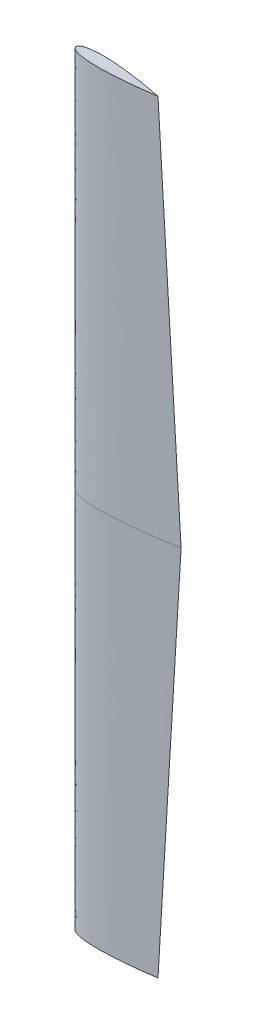
SolidWorks part; units mm, degrees
ref_plane "Front Plane" through (0, 0, 0) normal (0, 0, 1) x (1, 0, 0)
ref_plane "Top Plane" through (0, 0, 0) normal (0, 1, 0) x (1, 0, 0)
ref_plane "Right Plane" through (0, 0, 0) normal (1, 0, 0) x (0, 0, -1)
sketch "rootSketch" plane through (0, 0, 0) normal (0, 1, 0) x (1, 0, 0)
  line L0 (0, 0) -> (1500, 0) construction
  line L2 (137.5, -41.25) -> (137.5, 41.25) construction
  line L3 (0, 0) -> (550, 0) construction
  spline S0 degree 4 poles (0, 0) (-0.0002, 0.5984) (0.0567, 1.5657) (0.2758, 2.9641) (0.8226, 4.783) (1.5554, 6.4718) (2.6286, 8.3132) (4.15, 10.3394) (6.3375, 12.6439) (9.5808, 15.3558) (14.4955, 18.5934) (21.9815, 22.4137) (33.5898, 26.8869) (51.0146, 31.717) (76.9525, 36.5218) (110.4071, 39.9858) (144.1442, 41.3457) (175.9798, 41.3412) (207.8008, 40.5208) (234.2981, 39.2509) (260.7672, 37.5107) (287.2069, 35.3768) (308.3405, 33.4599) (329.4561, 31.3537) (350.5537, 29.0753) (368.9985, 26.9421) (384.7971, 25.0199) (397.955, 23.3576) (408.477, 21.9921) (421.6232, 20.2411) (437.39, 18.0697) (455.7689, 15.4347) (476.7548, 12.281) (495.0946, 9.3938) (509.495, 7.0363) (519.9529, 5.2764) (525.8458, 4.2686) (529.7425, 3.5958) (533.0627, 3.0173) (535.5459, 2.5832) (539.1156, 1.9525) (542.393, 1.3729) (547.5735, 0.4408) (550.9027, -0.1629) (555.289, -0.9656) (558.5613, -1.5705) (562.0766, -2.2247) (565.4861, -2.8651) (569.8025, -3.6822) (574.9524, -4.6683) (580.9745, -5.8375) (587.8418, -7.1939) (594.7112, -8.5743) (599.8557, -9.6263) (603.2861, -10.3361) (604.9999, -10.6929) knots 0 0 0 0 0 0.003841 0.006235 0.009072 0.012193 0.015657 0.019917 0.025339 0.032593 0.042799 0.057705 0.079311 0.112503 0.158973 0.227236 0.2955 0.329632 0.363764 0.432028 0.46616 0.500292 0.534424 0.568556 0.602688 0.63682 0.653886 0.670952 0.688018 0.705084 0.739215 0.773347 0.807479 0.841611 0.858677 0.86721 0.875743 0.88001 0.884276 0.888543 0.892809 0.901342 0.909875 0.915508 0.921141 0.926774 0.932406 0.938039 0.943672 0.954938 0.966203 0.977469 0.988734 1 1 1 1 1 construction
  spline S1 degree 4 poles (0, 0) (-0.0002, 0.5984) (0.0567, 1.5657) (0.2758, 2.9641) (0.8226, 4.783) (1.5554, 6.4718) (2.6286, 8.3132) (4.15, 10.3394) (6.3375, 12.6439) (9.5808, 15.3558) (14.4955, 18.5934) (21.9815, 22.4137) (33.5898, 26.8869) (51.0146, 31.717) (76.9525, 36.5218) (110.4071, 39.9858) (144.1442, 41.3457) (175.9798, 41.3412) (207.8008, 40.5208) (234.2981, 39.2509) (260.7672, 37.5107) (287.2069, 35.3768) (308.3405, 33.4599) (329.4561, 31.3537) (350.5537, 29.0753) (368.9985, 26.9421) (384.7971, 25.0199) (397.955, 23.3576) (408.477, 21.9921) (421.6232, 20.2411) (437.39, 18.0697) (455.7689, 15.4347) (476.7548, 12.281) (495.0946, 9.3938) (509.495, 7.0363) (519.9529, 5.2764) (525.8458, 4.2686) (529.7425, 3.5958) (533.0627, 3.0173) (535.5459, 2.5832) (539.1156, 1.9525) (542.393, 1.3729) (546.4913, 0.6355) (548.8127, 0.2157) (550, 0) knots 0 0 0 0 0 0.003841 0.006235 0.009072 0.012193 0.015657 0.019917 0.025339 0.032593 0.042799 0.057705 0.079311 0.112503 0.158973 0.227236 0.2955 0.329632 0.363764 0.432028 0.46616 0.500292 0.534424 0.568556 0.602688 0.63682 0.653886 0.670952 0.688018 0.705084 0.739215 0.773347 0.807479 0.841611 0.858677 0.86721 0.875743 0.88001 0.884276 0.888543 0.892809 0.901342 0.909875 0.909875 0.909875 0.909875 0.909875
  spline S2 degree 4 poles (0, 0) (-0.0002, -0.5984) (0.0567, -1.5657) (0.2758, -2.9641) (0.8226, -4.783) (1.5554, -6.4718) (2.6286, -8.3132) (4.15, -10.3394) (6.3375, -12.6439) (9.5808, -15.3558) (14.4955, -18.5934) (21.9815, -22.4137) (33.5898, -26.8869) (51.0146, -31.717) (76.9525, -36.5218) (110.4071, -39.9858) (144.1442, -41.3457) (175.9798, -41.3412) (207.8008, -40.5208) (234.2981, -39.2509) (260.7672, -37.5107) (287.2069, -35.3768) (308.3405, -33.4599) (329.4561, -31.3537) (350.5537, -29.0753) (368.9985, -26.9421) (384.7971, -25.0199) (397.955, -23.3576) (408.477, -21.9921) (421.6232, -20.2411) (437.39, -18.0697) (455.7689, -15.4347) (476.7548, -12.281) (495.0946, -9.3938) (509.495, -7.0363) (519.9529, -5.2764) (525.8458, -4.2686) (529.7425, -3.5958) (533.0627, -3.0173) (535.5459, -2.5832) (539.1156, -1.9525) (542.393, -1.3729) (547.5735, -0.4408) (550.9027, 0.1629) (555.289, 0.9656) (558.5613, 1.5705) (562.0766, 2.2247) (565.4861, 2.8651) (569.8025, 3.6822) (574.9524, 4.6683) (580.9745, 5.8375) (587.8418, 7.1939) (594.7112, 8.5743) (599.8557, 9.6263) (603.2861, 10.3361) (604.9999, 10.6929) knots 0 0 0 0 0 0.003841 0.006235 0.009072 0.012193 0.015657 0.019917 0.025339 0.032593 0.042799 0.057705 0.079311 0.112503 0.158973 0.227236 0.2955 0.329632 0.363764 0.432028 0.46616 0.500292 0.534424 0.568556 0.602688 0.63682 0.653886 0.670952 0.688018 0.705084 0.739215 0.773347 0.807479 0.841611 0.858677 0.86721 0.875743 0.88001 0.884276 0.888543 0.892809 0.901342 0.909875 0.915508 0.921141 0.926774 0.932406 0.938039 0.943672 0.954938 0.966203 0.977469 0.988734 1 1 1 1 1 construction
  spline S3 degree 4 poles (0, 0) (-0.0002, -0.5984) (0.0567, -1.5657) (0.2758, -2.9641) (0.8226, -4.783) (1.5554, -6.4718) (2.6286, -8.3132) (4.15, -10.3394) (6.3375, -12.6439) (9.5808, -15.3558) (14.4955, -18.5934) (21.9815, -22.4137) (33.5898, -26.8869) (51.0146, -31.717) (76.9525, -36.5218) (110.4071, -39.9858) (144.1442, -41.3457) (175.9798, -41.3412) (207.8008, -40.5208) (234.2981, -39.2509) (260.7672, -37.5107) (287.2069, -35.3768) (308.3405, -33.4599) (329.4561, -31.3537) (350.5537, -29.0753) (368.9985, -26.9421) (384.7971, -25.0199) (397.955, -23.3576) (408.477, -21.9921) (421.6232, -20.2411) (437.39, -18.0697) (455.7689, -15.4347) (476.7548, -12.281) (495.0946, -9.3938) (509.495, -7.0363) (519.9529, -5.2764) (525.8458, -4.2686) (529.7425, -3.5958) (533.0627, -3.0173) (535.5459, -2.5832) (539.1156, -1.9525) (542.393, -1.3729) (546.4913, -0.6355) (548.8127, -0.2157) (550, 0) knots 0 0 0 0 0 0.003841 0.006235 0.009072 0.012193 0.015657 0.019917 0.025339 0.032593 0.042799 0.057705 0.079311 0.112503 0.158973 0.227236 0.2955 0.329632 0.363764 0.432028 0.46616 0.500292 0.534424 0.568556 0.602688 0.63682 0.653886 0.670952 0.688018 0.705084 0.739215 0.773347 0.807479 0.841611 0.858677 0.86721 0.875743 0.88001 0.884276 0.888543 0.892809 0.901342 0.909875 0.909875 0.909875 0.909875 0.909875
  point P10 (137.5, 0)
  dimension "incidenceAngle" = 0
  dimension "rootChord" = 550
  dimension "rootQuarterChord" = 137.5
  dimension "rootMaxThickness" = 82.5
ref_plane "Plane1" through (0, 1999.998, 0) normal (0, 1, 0) x (1, 0, 0)
sketch "tipSketch" plane through (0, 1999.998, 0) normal (0, 1, 0) x (1, 0, 0)
  line L0 (218.7894, 0) -> (520.1012, 0) construction
  line L3 (0, 0) -> (439.861, -11.0572) construction
  line L4 (109.136, -35.7539) -> (110.7946, 30.2253) construction
  spline S0 degree 4 poles (0, 0) (-0.0002, 0.4799) (0.0456, 1.2558) (0.2213, 2.3695) (0.6579, 3.8074) (1.2415, 5.1394) (2.0932, 6.583) (3.2989, 8.1632) (5.0276, 9.9467) (7.5719, 12.0224) (11.4477, 14.4998) (17.3746, 17.4012) (26.5746, 20.7437) (40.3867, 24.2587) (61.0632, 27.6137) (87.8004, 29.7482) (119.0763, 30.2504) (148.9069, 29.2696) (174.4344, 27.6771) (195.6772, 25.9397) (212.6521, 24.3361) (229.6081, 22.5432) (246.5456, 20.5825) (263.4645, 18.4705) (280.3662, 16.221) (295.1391, 14.1416) (307.7921, 12.2843) (318.327, 10.6888) (326.7541, 9.3833) (337.2749, 7.7178) (349.9046, 5.6607) (364.6022, 3.1846) (381.4182, 0.2341) (396.0609, -2.4384) (408.6785, -4.8221) (419.0533, -6.8347) (426.5408, -8.32) (432.4883, -9.518) (438.6715, -10.7845) (442.4872, -11.5748) (448.6722, -12.8694) (453.5332, -13.9082) (459.43, -15.1786) (464.6859, -16.3343) (470.343, -17.5913) (475.7161, -18.8084) (479.9213, -19.772) (482.6133, -20.398) (484.0029, -20.7217) knots 0 0 0 0 0 0.003846 0.006245 0.009023 0.012045 0.015501 0.01968 0.024954 0.031954 0.041824 0.056556 0.077861 0.110456 0.156157 0.224645 0.293132 0.36162 0.395864 0.430108 0.464352 0.498596 0.53284 0.567084 0.601327 0.635571 0.652693 0.669815 0.686937 0.704059 0.738303 0.772547 0.806791 0.841035 0.858157 0.875279 0.892401 0.900962 0.909523 0.920832 0.932142 0.943452 0.954761 0.966071 0.977381 0.98869 1 1 1 1 1 construction
  spline S1 degree 4 poles (0, 0) (-0.0002, 0.4799) (0.0456, 1.2558) (0.2213, 2.3695) (0.6579, 3.8074) (1.2415, 5.1394) (2.0932, 6.583) (3.2989, 8.1632) (5.0276, 9.9467) (7.5719, 12.0224) (11.4477, 14.4998) (17.3746, 17.4012) (26.5746, 20.7437) (40.3867, 24.2587) (61.0632, 27.6137) (87.8004, 29.7482) (119.0763, 30.2504) (148.9069, 29.2696) (174.4344, 27.6771) (195.6772, 25.9397) (212.6521, 24.3361) (229.6081, 22.5432) (246.5456, 20.5825) (263.4645, 18.4705) (280.3662, 16.221) (295.1391, 14.1416) (307.7921, 12.2843) (318.327, 10.6888) (326.7541, 9.3833) (337.2749, 7.7178) (349.9046, 5.6607) (364.6022, 3.1846) (381.4182, 0.2341) (396.0609, -2.4384) (408.6785, -4.8221) (419.0533, -6.8347) (426.5408, -8.32) (432.4883, -9.518) (437.1364, -10.47) (439.0509, -10.8644) (440, -11.0607) knots 0 0 0 0 0 0.003846 0.006245 0.009023 0.012045 0.015501 0.01968 0.024954 0.031954 0.041824 0.056556 0.077861 0.110456 0.156157 0.224645 0.293132 0.36162 0.395864 0.430108 0.464352 0.498596 0.53284 0.567084 0.601327 0.635571 0.652693 0.669815 0.686937 0.704059 0.738303 0.772547 0.806791 0.841035 0.858157 0.875279 0.892401 0.900962 0.909523 0.909523 0.909523 0.909523 0.909523
  spline S2 degree 4 poles (0, 0) (-0.0243, -0.4792) (-0.0175, -1.2565) (0.102, -2.3776) (0.4657, -3.8356) (0.9817, -5.1953) (1.7598, -6.6799) (2.8846, -8.3186) (4.5214, -10.1867) (6.9583, -12.3877) (10.7048, -15.0566) (16.4783, -18.2522) (25.4988, -22.0527) (39.1168, -26.2572) (59.5987, -30.6469) (86.1948, -34.1221) (117.406, -36.1951) (147.2482, -36.7144) (172.8235, -36.4064) (194.1267, -35.7386) (211.1608, -34.99) (228.1855, -34.0512) (245.2, -32.944) (262.2037, -31.6848) (279.1971, -30.2873) (294.0558, -28.9528) (306.7861, -27.7336) (317.3879, -26.6694) (325.8699, -25.789) (336.4611, -24.6542) (349.1782, -23.2343) (363.9817, -21.4998) (380.9247, -19.3979) (395.6832, -17.4645) (408.4046, -15.7178) (418.8674, -14.229) (426.4201, -13.1218) (432.4203, -12.2241) (438.6593, -11.2699) (442.5099, -10.6723) (448.7521, -9.6901) (453.6592, -8.8968) (459.6124, -7.9243) (464.9197, -7.0341) (470.6328, -6.063) (476.0602, -5.1174) (480.3086, -4.3663) (483.0286, -3.8763) (484.4327, -3.6229) knots 0 0 0 0 0 0.003846 0.006245 0.009023 0.012045 0.015501 0.01968 0.024954 0.031954 0.041824 0.056556 0.077861 0.110456 0.156157 0.224645 0.293132 0.36162 0.395864 0.430108 0.464352 0.498596 0.53284 0.567084 0.601327 0.635571 0.652693 0.669815 0.686937 0.704059 0.738303 0.772547 0.806791 0.841035 0.858157 0.875279 0.892401 0.900962 0.909523 0.920832 0.932142 0.943452 0.954761 0.966071 0.977381 0.98869 1 1 1 1 1 construction
  spline S3 degree 4 poles (0, 0) (-0.0243, -0.4792) (-0.0175, -1.2565) (0.102, -2.3776) (0.4657, -3.8356) (0.9817, -5.1953) (1.7598, -6.6799) (2.8846, -8.3186) (4.5214, -10.1867) (6.9583, -12.3877) (10.7048, -15.0566) (16.4783, -18.2522) (25.4988, -22.0527) (39.1168, -26.2572) (59.5987, -30.6469) (86.1948, -34.1221) (117.406, -36.1951) (147.2482, -36.7144) (172.8235, -36.4064) (194.1267, -35.7386) (211.1608, -34.99) (228.1855, -34.0512) (245.2, -32.944) (262.2037, -31.6848) (279.1971, -30.2873) (294.0558, -28.9528) (306.7861, -27.7336) (317.3879, -26.6694) (325.8699, -25.789) (336.4611, -24.6542) (349.1782, -23.2343) (363.9817, -21.4998) (380.9247, -19.3979) (395.6832, -17.4645) (408.4046, -15.7178) (418.8674, -14.229) (426.4201, -13.1218) (432.4203, -12.2241) (437.1103, -11.5068) (439.0422, -11.2091) (440, -11.0607) knots 0 0 0 0 0 0.003846 0.006245 0.009023 0.012045 0.015501 0.01968 0.024954 0.031954 0.041824 0.056556 0.077861 0.110456 0.156157 0.224645 0.293132 0.36162 0.395864 0.430108 0.464352 0.498596 0.53284 0.567084 0.601327 0.635571 0.652693 0.669815 0.686937 0.704059 0.738303 0.772547 0.806791 0.841035 0.858157 0.875279 0.892401 0.900962 0.909523 0.909523 0.909523 0.909523 0.909523
  point P10 (109.9653, -2.7643)
  dimension "incidenceAngle" = 1.44
  dimension "tipChord" = 440
  dimension "tipQuarterChord" = 110
  dimension "tipMaxThickness" = 66
  dimension "sweepOffset" = 0
loft "Loft1" add profiles "rootSketch", "tipSketch" connector at (0, 0, 0) connector at (0, 1999.998, 0)
mirror "Mirror1" about plane through (0, 0, 0) normal (0, 1, 0) of "Loft1"
ref_plane "Plane2" through (550, 0, 0) normal (1, 0, 0) x (0, 0, -1)
sketch "elevatorSketch" plane through (0, 0, 0) normal (0, 0, 1) x (1, 0, 0)
  line L0 (333.9978, 0.1319) -> (284.6342, 1495.9985)
  line L1 (0, 1499.9985) -> (280.5, 1499.9985) construction
  line L2 (0, 0) -> (330, 0) construction
  line L3 (0, 0) -> (550, 0) construction
  line L4 (330, 0) -> (280.5, 1499.9985)
  line L5 (284.6342, 1495.9985) -> (830.5, 1495.9985)
  line L7 (280.5, 1499.9985) -> (830.5, 1499.9985)
  line L8 (330, 0) -> (333.9978, 0.1319)
  line L9 (830.5, 1499.9985) -> (830.5, 1495.9985)
  dimension "elevatorEndyLoc" = 1499.9985
  dimension "elevatorEndxLoc" = 280.5
  dimension "D1" = 330
  dimension "D2" = 550
  dimension "D3" = 4
extrude "Cut-Extrude2" [suppressed] cut sketch "elevatorSketch" against normal blind 200 and the other way blind 200 contours L0 L5 L9 L7 L4 L8
mirror "Mirror2" [suppressed] about plane through (0, 0, 0) normal (0, 1, 0)
equation "\"rootChord@rootSketch\"=(\"rootChord\"+\"rootChord\")/2"
equation "\"rootQuarterChord@rootSketch\" = \"rootChord@rootSketch\" / 4"
equation "\"rootMaxThickness@rootSketch\" = \"rootChord\" * \"NACAairfoil\" / 100"
equation "\"halfSpan@Plane1\"=\"halfSpan\""
equation "\"tipQuarterChord@tipSketch\"=\"tipChord@tipSketch\"/4"
equation "\"tipMaxThickness@tipSketch\"=\"tipChord@tipSketch\"*\"NACAairfoil\"/100"
equation "\"rootChord@Plane2\"=\"rootChord@rootSketch\""
equation "\"elevatorWidth\"= 0.75'Elevator width as a percentage of H-stab span"
equation "\"elevatorEndyLoc@elevatorSketch\"=\"elevatorWidth\"*\"halfSpan@Plane1\""
equation "\"elevatorEndxLoc@elevatorSketch\"=\"elevatorEndyLoc@elevatorSketch\" * tan ( \"sweepAngle\" )  + 0.6 *  ( \"rootChord@rootSketch\" + \"elevatorEndyLoc@elevatorSketch\" *  (  (  ( \"tipChord@tipSketch\" - \"rootChord@rootSketch\" )  / \"halfSpan@Plane1\" )  )  )"
equation "\"D1@elevatorSketch\"=0.6*\"rootChord@rootSketch\""
equation "\"D2@elevatorSketch\"=1*\"rootChord@rootSketch\""
equation "\"D3@elevatorSketch\" = \"halfSpan\" / 500"
equation "\"halfSpan\"= \"rootChord\" * ( 1 + \"taperRatio\" ) / 2 * \"aspectRatio\" / 2'H-stab half Span"
equation "\"sweepOffset@tipSketch\" = \"halfSpan\" * tan ( \"sweepAngle\" ) "
equation "\"incidenceAngle@rootSketch\"=\"incidentAngle\""
equation "\"tipChord@tipSketch\"=\"rootChord\"*\"taperRatio\""
equation "\"rootChord\"= 0.55"
equation "\"NACAairfoil\"= 0015"
equation "\"incidentAngle\"= 0"
equation "\"aspectRatio\"= 8.0808"
equation "\"taperRatio\"= 0.8"
equation "\"sweepAngle\"= 0"
